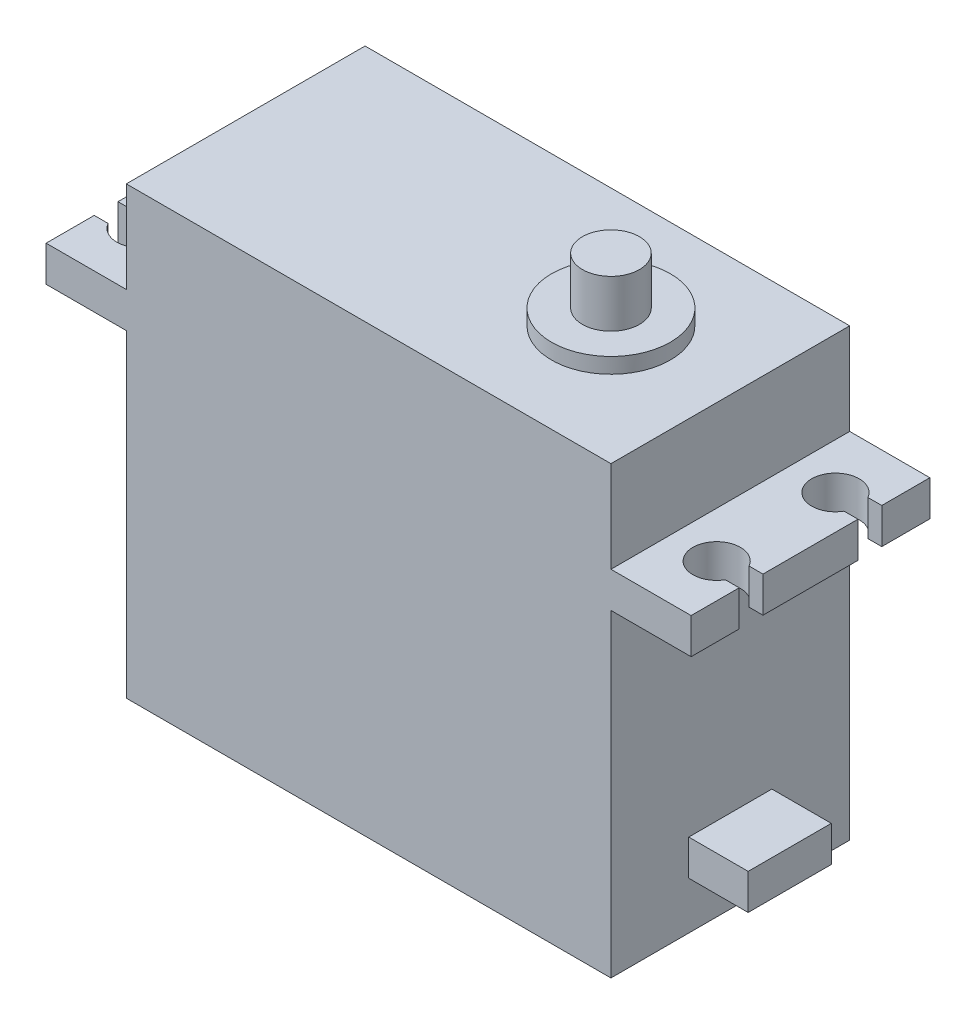
SolidWorks part; units mm, degrees
ref_plane "Front Plane" through (0, 0, 0) normal (0, 0, 1) x (1, 0, 0)
ref_plane "Top Plane" through (0, 0, 0) normal (0, 1, 0) x (1, 0, 0)
ref_plane "Right Plane" through (0, 0, 0) normal (1, 0, 0) x (0, 0, -1)
sketch "Sketch2" plane through (0, 0, 0) normal (0, 1, 0) x (1, 0, 0)
  line L0 (0, 0) -> (0, 10.05) construction
  line L1 (0, 0) -> (10.05, 0) construction
  line L2 (0, 0) -> (0, -10.05) construction
  line L3 (0, 0) -> (-30.75, 0) construction
  line L4 (-34.6, 5) -> (-34.6, -5) construction
  line L5 (-30.75, 10.05) -> (10.05, 10.05)
  line L6 (-30.75, 10.05) -> (-30.75, -10.05)
  line L7 (-30.75, -10.05) -> (10.05, -10.05)
  line L8 (10.05, 10.05) -> (10.05, -10.05)
  line L9 (-30.75, 10.05) -> (-37.5, 10.05) construction
  line L10 (-37.5, 10.05) -> (-37.5, -10.05) construction
  line L11 (-37.5, -10.05) -> (-30.75, -10.05) construction
  line L12 (-10.35, 10.05) -> (-10.35, -10.05) construction
  line L13 (13.9, 5) -> (13.9, -5) construction
  line L14 (-36.6, 5) -> (-37.5, 5) construction
  line L15 (10.05, 10.05) -> (16.8, 10.05) construction
  line L16 (16.8, 10.05) -> (16.8, -10.05) construction
  line L17 (16.8, -10.05) -> (10.05, -10.05) construction
  line L18 (10.05, 3.5) -> (15.05, 3.5) construction
  line L19 (15.05, 3.5) -> (15.05, -3.5) construction
  line L20 (15.05, -3.5) -> (10.05, -3.5) construction
  circle A0 centre (0, 0) radius 2.4
  circle A1 centre (0, 0) radius 10.05 construction
  circle A2 centre (-34.6, 5) radius 2
  circle A3 centre (-34.6, -5) radius 2
  circle A4 centre (13.9, -5) radius 2
  circle A5 centre (13.9, 5) radius 2
  circle A6 centre (0, 0) radius 5 construction
  dimension "D1" = 4.8
  dimension "D6" = 4
  dimension "D8" = 10
  dimension "D2" = 40.8
  dimension "D3" = 20.1
  dimension "D4" = 10
  dimension "D5" = 48.5
  dimension "D7" = 0.9
  dimension "D9" = 54.3
  dimension "D10" = 7
  dimension "D11" = 5
sketch "Sketch3" plane through (0, 0, 0) normal (0, 0, 1) x (1, 0, 0)
  line L0 (-30.75, 0) -> (-30.75, 26.8)
  line L1 (-30.75, 26.8) -> (-37.5, 26.8)
  line L2 (-37.5, 26.8) -> (-37.5, 29.8)
  line L3 (-37.5, 29.8) -> (-30.75, 29.8)
  line L4 (-30.75, 29.8) -> (-30.75, 37.5)
  line L5 (-30.75, 37.5) -> (10.05, 37.5)
  line L6 (10.05, 37.5) -> (10.05, 29.8)
  line L7 (10.05, 29.8) -> (16.8, 29.8)
  line L8 (16.8, 29.8) -> (16.8, 26.8)
  line L9 (16.8, 26.8) -> (10.05, 26.8)
  line L10 (10.05, 26.8) -> (10.05, 0)
  line L11 (10.05, 0) -> (-30.75, 0)
  line L12 (-10.35, 0) -> (-10.35, 37.5) construction
  line L13 (2.4, 0) -> (2.4, 42.8) construction
  line L14 (2.4, 0) -> (-2.4, 0) construction
  line L15 (2.4, 42.8) -> (-2.4, 42.8) construction
  line L16 (-2.4, 42.8) -> (-2.4, 0) construction
  line L17 (10.05, 0) -> (-10.05, 0) construction
  line L18 (-5, 38.8) -> (5, 38.8) construction
  line L19 (-5, 0) -> (-5, 38.8) construction
  line L20 (5, 38.8) -> (5, 0) construction
  line L21 (10.05, 4) -> (15.05, 4) construction
  line L22 (15.05, 4) -> (15.05, 7) construction
  line L23 (15.05, 7) -> (10.05, 7) construction
  dimension "D1" = 26.8
  dimension "D2" = 3
  dimension "D3" = 4
  dimension "D4" = 38.8
  dimension "D5" = 1.3
  dimension "D6" = 12
  dimension "D7" = 7
  dimension "D8" = 4
  dimension "D9" = 37.5
extrude "Boss-Extrude1" add sketch "Sketch3" along normal up to vertex (10.05 mm away) from vertex up to point (-30.75, 0, 10.05) starting at point (-30.75, 0, -10.05)
sketch "Sketch4" plane through (0, 29.8, 0) normal (0, 1, 0) x (1, 0, 0)
  line L0 (-10.35, 10.05) -> (-10.35, -10.05) construction
  line L1 (-10.35, 10.05) -> (-10.35, -10.05) construction
  line L2 (-37.5, 10.05) -> (-37.5, -10.05) construction
  line L4 (-37.5, 6) -> (-37.5, 4)
  line L5 (16.8, -6) -> (15.6321, -6)
  line L6 (-10.35, 0) -> (-37.5, 0) construction
  line L7 (-37.5, 4) -> (-36.3321, 4)
  line L8 (-37.5, 6) -> (-36.3321, 6)
  line L9 (-34.6, 5) -> (-37.5, 5) construction
  line L10 (-37.5, -4) -> (-37.5, -6)
  line L11 (-37.5, -4) -> (-36.3321, -4)
  line L12 (-37.5, -6) -> (-36.3321, -6)
  line L13 (16.8, -4) -> (16.8, -6)
  line L14 (16.8, -4) -> (15.6321, -4)
  line L15 (16.8, 4) -> (15.6321, 4)
  line L16 (16.8, 6) -> (16.8, 4)
  line L17 (16.8, 6) -> (15.6321, 6)
  circle A0 centre (-34.6, -5) radius 2 construction
  circle A1 centre (-34.6, 5) radius 2 construction
  circle A2 centre (13.9, 5) radius 2 construction
  circle A3 centre (13.9, -5) radius 2 construction
  arc A4 (-36.3321, -6) -> (-36.3321, -4) centre (-34.6, -5) ccw
  arc A5 (-36.3321, 4) -> (-36.3321, 6) centre (-34.6, 5) ccw
  arc A6 (15.6321, 6) -> (15.6321, 4) centre (13.9, 5) ccw
  arc A7 (15.6321, -4) -> (15.6321, -6) centre (13.9, -5) ccw
  dimension "D1" = 2
extrude "Cut-Extrude1" cut sketch "Sketch4" against normal through all
sketch "Sketch5" plane through (0, 37.5, 0) normal (0, 1, 0) x (1, 0, 0)
  circle A0 centre (0, 0) radius 5 construction
  circle A1 centre (0, 0) radius 5
extrude "Boss-Extrude2" add sketch "Sketch5" along normal up to vertex (1.3 mm away) up to point (-5, 38.8, 0)
sketch "Sketch6" plane through (0, 38.8, 0) normal (0, 1, 0) x (1, 0, 0)
  circle A0 centre (0, 0) radius 2.4 construction
  circle A1 centre (0, 0) radius 2.4
extrude "Boss-Extrude3" add sketch "Sketch6" along normal up to vertex (4 mm away) up to point (-2.4, 42.8, 0)
sketch "Sketch7" plane through (0, 38.8, 0) normal (0, 1, 0) x (1, 0, 0)
  circle A0 centre (0, 0) radius 2.85
  dimension "D1" = 5.7
sketch "Sketch8" plane through (10.05, 0, 0) normal (1, 0, 0) x (0, 0, -1)
  line L1 (-3.5, 7) -> (3.5, 7)
  line L2 (-3.5, 7) -> (-3.5, 4)
  line L3 (-3.5, 4) -> (3.5, 4)
  line L4 (3.5, 7) -> (3.5, 4)
extrude "Boss-Extrude4" add sketch "Sketch8" along normal up to vertex (5 mm away) up to point (15.05, 7, 0)
